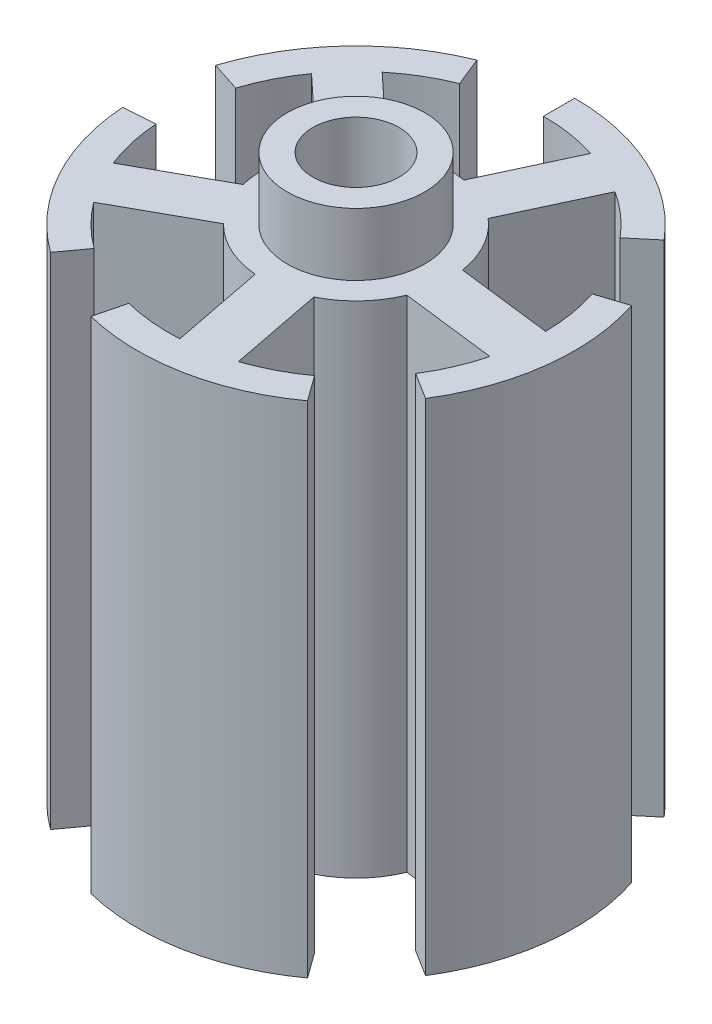
SolidWorks part; units mm, degrees
ref_plane "Front Plane" through (0, 0, 0) normal (0, 0, 1) x (1, 0, 0)
ref_plane "Top Plane" through (0, 0, 0) normal (0, 1, 0) x (1, 0, 0)
ref_plane "Right Plane" through (0, 0, 0) normal (1, 0, 0) x (0, 0, -1)
sketch "Sketch1" plane through (0, 0, 0) normal (0, 1, 0) x (1, 0, 0)
  line L0 (0, 17.5) -> (0, 15)
  line L1 (11.4907, 9.6418) -> (13.4058, 11.2488)
  line L2 (16.6435, 5.4078) -> (14.2658, 4.6353)
  line L3 (12.7207, -7.9488) -> (14.8408, -9.2736)
  line L4 (10.2862, -14.1578) -> (8.8168, -12.1353)
  line L5 (-3.6288, -14.5544) -> (-4.2336, -16.9802)
  line L6 (-10.2862, -14.1578) -> (-8.8168, -12.1353)
  line L7 (-14.9635, -1.0463) -> (-17.4574, -1.2207)
  line L8 (-16.6435, 5.4078) -> (-14.2658, 4.6353)
  line L9 (-5.6191, 13.9078) -> (-6.5556, 16.2257)
  arc A0 (0, 17.5) -> (13.4058, 11.2488) centre (0, 0) cw
  arc A1 (11.4907, 9.6418) -> (0, 15) centre (0, 0) ccw
  arc A2 (16.6435, 5.4078) -> (14.8408, -9.2736) centre (0, 0) cw
  arc A3 (12.7207, -7.9488) -> (14.2658, 4.6353) centre (0, 0) ccw
  arc A4 (10.2862, -14.1578) -> (-4.2336, -16.9802) centre (0, 0) cw
  arc A5 (-3.6288, -14.5544) -> (8.8168, -12.1353) centre (0, 0) ccw
  arc A6 (-10.2862, -14.1578) -> (-17.4574, -1.2207) centre (0, 0) cw
  arc A7 (-14.9635, -1.0463) -> (-8.8168, -12.1353) centre (0, 0) ccw
  arc A8 (-16.6435, 5.4078) -> (-6.5556, 16.2257) centre (0, 0) cw
  arc A9 (-5.6191, 13.9078) -> (-14.2658, 4.6353) centre (0, 0) ccw
  point P25 (0, 0)
  dimension "D1" = 5
extrude "Boss-Extrude2" add sketch "Sketch1" along normal blind 40
sketch "Sketch2" plane through (0, 0, 0) normal (0, 1, 0) x (1, 0, 0)
  line L0 (8.1519, 12.7494) -> (4.5267, 14.4399)
  line L1 (8.1519, 12.7494) -> (1.8723, -0.7172)
  line L2 (4.5267, 14.4399) -> (-1.7529, 0.9732)
  line L3 (1.8723, -0.7172) -> (-1.7529, 0.9732)
  line L4 (14.6445, -3.8131) -> (15.1319, 0.1571)
  line L5 (14.6445, -3.8131) -> (-0.1036, -2.0023)
  line L6 (15.1319, 0.1571) -> (0.3839, 1.9679)
  line L7 (-0.1036, -2.0023) -> (0.3839, 1.9679)
  line L8 (0.8989, -15.106) -> (4.8254, -14.3428)
  line L9 (0.8989, -15.106) -> (-1.9363, -0.5203)
  line L10 (4.8254, -14.3428) -> (1.9902, 0.243)
  line L11 (-1.9363, -0.5203) -> (1.9902, 0.243)
  line L12 (-14.0889, -5.5229) -> (-12.1497, -9.0214)
  line L13 (-14.0889, -5.5229) -> (-1.0931, 1.6808)
  line L14 (-12.1497, -9.0214) -> (0.8461, -1.8177)
  line L15 (-1.0931, 1.6808) -> (0.8461, -1.8177)
  line L16 (-9.6063, 11.6927) -> (-12.3343, 8.7673)
  line L17 (-9.6063, 11.6927) -> (1.2607, 1.559)
  line L18 (-12.3343, 8.7673) -> (-1.4673, -1.3664)
  line L19 (1.2607, 1.559) -> (-1.4673, -1.3664)
  arc A0 (11.4907, 9.6418) -> (0, 15) centre (0, 0) ccw construction
  point P8 (6.3393, 13.5946)
  point P27 (0, 0)
  dimension "D1" = 5
extrude "Boss-Extrude3" add sketch "Sketch2" along normal blind 40 contours L2 L17 L6 L1 L0 | L16 L18 L13 L2 L17 | L18 L13 L12 L14 L9 | L14 L9 L8 L10 L5 | L10 L5 L4 L6 L1 | L7 L15 L14 L5 L10 L1 L3 L11 | L19 L17 L6 L7 | L17 L19 L7 L3 L11 L10 L1 L6 | L19 L7 L6 L17 L2 L13 L15 L3 | L15 L13 L2 L3 | L11 L3 L1 L10 | L11 L19 L18 L9 L14 L5 L7 L15 | L19 L15 L3 L2 L13 L18 L9 L11 | L19 L11 L9 L18 | L15 L7 L5 L14 | L7 L6 L4 L5 | L2 L3 L1 L0 | L15 L14 L12 L13 region at (3.6821, 0, -7.8962) region at (8.6476, 0, 1.0618) region at (1.5876, 0, -0.88) region at (-0.3464, 0, -1.7818) region at (-6.3719, 0, -5.9419) region at (1.3275, 0, 1.2379) region at (1.4907, 0, 0.183) region at (0.6347, 0, -1.3612) region at (-1.0984, 0, -1.0243) region at (-1.8016, 0, -0.2212) region at (1.6624, 0, 8.5524) region at (-7.6201, 0, 4.2239) region at (-0.7671, 0, 1.6451) region at (0.2866, 0, 1.4743) region at (-1.3136, 0, 0.7281)
sketch "Sketch3" plane through (0, 0, 0) normal (0, 1, 0) x (1, 0, 0)
  circle A0 centre (0, 0) radius 7.5
extrude "Boss-Extrude4" add sketch "Sketch3" along normal blind 40
ref_plane "Plane2" through (0, 40, 0) normal (0, 1, 0) x (1, 0, 0)
sketch "Sketch5" plane through (0, 40, 0) normal (0, 1, 0) x (1, 0, 0)
  circle A0 centre (0, 0) radius 5.5
extrude "Boss-Extrude5" add sketch "Sketch5" along normal blind 5
sketch "Sketch4" plane through (0, 0, 0) normal (0, 1, 0) x (1, 0, 0)
  circle A0 centre (0, 0) radius 3.45
extrude "Cut-Extrude1" cut sketch "Sketch4" along normal blind 45
